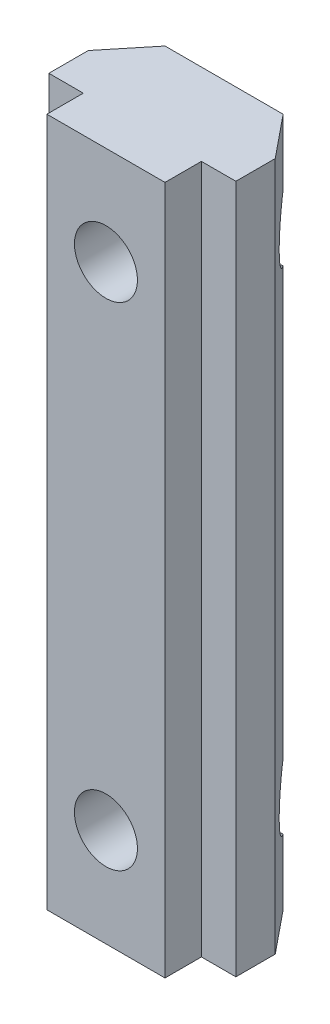
SolidWorks part; units mm, degrees
ref_plane "Спереди" through (0, 0, 0) normal (0, 0, 1) x (1, 0, 0)
ref_plane "Сверху" through (0, 0, 0) normal (0, 1, 0) x (1, 0, 0)
ref_plane "Справа" through (0, 0, 0) normal (1, 0, 0) x (0, 0, -1)
sketch "Sketch1" plane through (0, 0, 0) normal (0, 1, 0) x (1, 0, 0)
  line L2 (-3, 2.9786) -> (3, 2.9786)
  line L10 (-4.75, 6.8286) -> (-4.75, 4.8286)
  line L11 (-3, 8.9786) -> (-4.75, 6.8286)
  line L12 (3, 8.9786) -> (-3, 8.9786)
  line L13 (4.75, 6.8286) -> (3, 8.9786)
  line L14 (4.75, 4.8286) -> (4.75, 6.8286)
  line L15 (3, 4.8286) -> (4.75, 4.8286)
  line L16 (3, 2.9786) -> (3, 4.8286)
  line L17 (-3, 4.8286) -> (-3, 2.9786)
  line L18 (-4.75, 4.8286) -> (-3, 4.8286)
  point P0 (0, 8.9786)
  point P3 (0, 2.9786)
  dimension "D1" = 6
  dimension "D2" = 6
  dimension "D3" = 1.85
  dimension "D4" = 6
  dimension "D5" = 9.5
  dimension "D6" = 2
extrude "Extrude1" add sketch "Sketch1" along normal blind 35
sketch "Sketch2" plane through (0, 0, -8.9786) normal (0, 0, -1) x (-1, 0, 0)
  line L0 (-3, 0) -> (3, 35) construction
  line L1 (-3, 35) -> (3, 35) construction
  line L2 (3, 35) -> (3, 0) construction
  line L3 (0, 17.5) -> (0, 30) construction
  line L4 (0, 17.5) -> (9.4492, 17.5) construction
  line L5 (0, 33.3486) -> (-2.9, 31.6743)
  line L6 (-2.9, 31.6743) -> (-2.9, 28.3257)
  line L7 (-2.9, 28.3257) -> (0, 26.6514)
  line L8 (0, 26.6514) -> (2.9, 28.3257)
  line L9 (2.9, 28.3257) -> (2.9, 31.6743)
  line L10 (2.9, 31.6743) -> (0, 33.3486)
  line L11 (2.9, 3.3257) -> (0, 1.6514)
  line L12 (2.9, 6.6743) -> (2.9, 3.3257)
  line L13 (0, 8.3486) -> (2.9, 6.6743)
  line L14 (-2.9, 6.6743) -> (0, 8.3486)
  line L15 (-2.9, 3.3257) -> (-2.9, 6.6743)
  line L16 (0, 1.6514) -> (-2.9, 3.3257)
  circle A0 centre (0, 30) radius 1.6
  circle A1 centre (0, 30) radius 2.9 construction
  circle A2 centre (0, 5) radius 2.9 construction
  circle A3 centre (0, 5) radius 1.6
  dimension "D1" = 3.2
  dimension "D2" = 5.8
  dimension "D3" = 25
extrude "Extrude2" cut sketch "Sketch2" against normal up to next contours A0 | A3 region at (0, 30, -8.9786) region at (0, 5, -8.9786)
extrude "Extrude3" cut sketch "Sketch" against normal blind 3.5
sketch "Sketch" plane through (0, 0, -8.9786) normal (0, 0, -1) x (-1, 0, 0) same geometry as "Sketch2"
sketch "Sketch3" plane through (-2.9, 0, 0) normal (1, 0, 0) x (0, 0, -1)
  line L0 (8.9786, 31.6743) -> (8.9786, 28.3257)
  arc A0 (8.9786, 31.6743) -> (8.9786, 28.3257) centre (9.7606, 30) ccw
extrude "Extrude4" cut sketch "Sketch3" against normal up to next and the other way up to next
ref_plane "Plane1" through (0, 17.5, 0) normal (0, 1, 0) x (1, 0, 0)
mirror "Mirror1" about plane through (0, 17.5, 0) normal (0, 1, 0) of "Extrude4"
